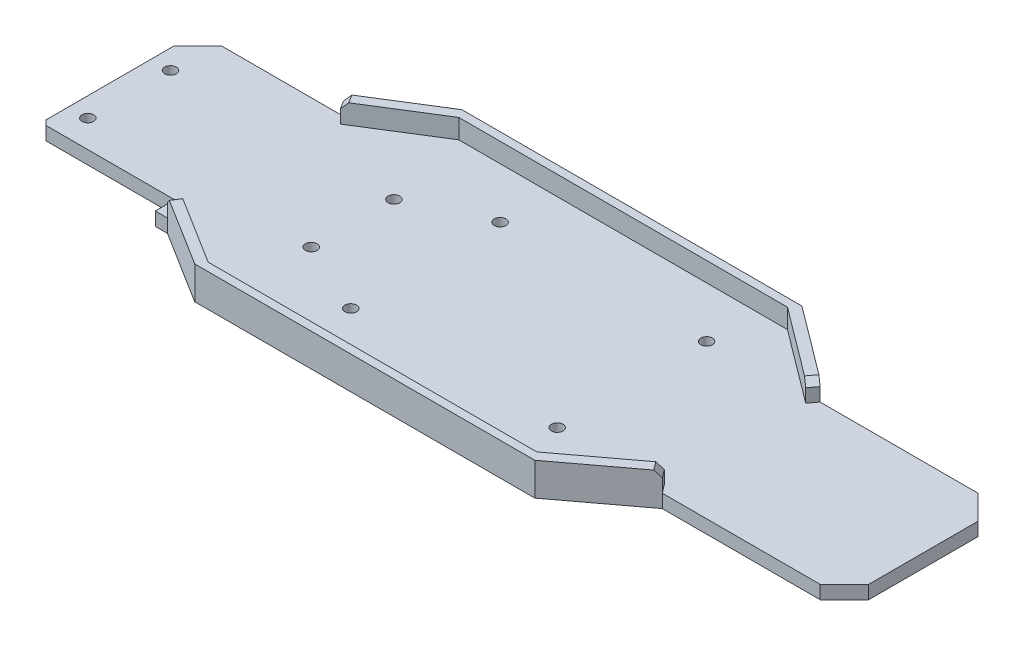
SolidWorks part; units mm, degrees
material "PETG - Polymaker"
ref_plane "Front Plane" through (0, 0, 0) normal (0, 0, 1) x (1, 0, 0)
ref_plane "Top Plane" through (0, 0, 0) normal (0, 1, 0) x (1, 0, 0)
ref_plane "Right Plane" through (0, 0, 0) normal (1, 0, 0) x (0, 0, -1)
sketch "Sketch1" plane through (0, 0, 0) normal (0, 1, 0) x (1, 0, 0)
  line L0 (-235.1499, 0) -> (235.1499, 0) construction
  line L1 (0, 0) -> (0, 52596.8311) construction
  line L2 (-100, 36.25) -> (-70, 55)
  line L3 (-70, 55) -> (70, 55)
  line L4 (-100, 36.25) -> (-160, 36.25)
  line L5 (-160, 36.25) -> (-160, -36.25)
  line L6 (-70, -55) -> (70, -55)
  line L7 (-100, -36.25) -> (-70, -55)
  line L8 (-100, -36.25) -> (-160, -36.25)
  line L9 (70, 55) -> (100, 32.5)
  line L10 (100, 32.5) -> (175, 32.5)
  line L11 (175, 32.5) -> (175, -32.5)
  line L12 (100, -32.5) -> (175, -32.5)
  line L13 (70, -55) -> (100, -32.5)
  point P3 (0, 0)
  point P10 (-85, 45.625)
  point P15 (-85, -45.625)
  point P18 (-160, 0)
  point P19 (0, -55)
  point P20 (0, 55)
  point P23 (175, 0)
  dimension "D1" = 55
  dimension "D2" = 72.5
  dimension "D3" = 30
  dimension "D4" = 60
  dimension "D5" = 140
  dimension "D6" = 75
  dimension "D7" = 65
  dimension "D8" = 30
  dimension "D9" = 110
extrude "Boss-Extrude1" add sketch "Sketch1" along normal blind 5.5
sketch "Sketch3" plane through (0, 5.5, 0) normal (0, 1, 0) x (1, 0, 0)
  line L0 (0, 0) -> (50000, 0) construction
  line L1 (0, 0) -> (0, 50000) construction
  line L2 (0, 55) -> (-70, 55)
  line L3 (70, 55) -> (-70, 55) construction
  line L4 (-70, 55) -> (-100, 36.25)
  line L5 (-100, 36.25) -> (-97.88, 32.858)
  line L6 (-97.88, 32.858) -> (-67.88, 51.608)
  line L7 (-67.88, 51.608) -> (0, 51.608)
  line L8 (-70, 55) -> (-67.88, 51.608) construction
  line L9 (0, 55) -> (70, 55)
  line L10 (70, 55) -> (100, 32.5)
  line L11 (100, 32.5) -> (97.456, 29.108)
  line L12 (97.456, 29.108) -> (67.456, 51.608)
  line L13 (67.456, 51.608) -> (0, 51.608)
  line L14 (67.456, 51.608) -> (70, 55) construction
  line L15 (67.456, -51.608) -> (70, -55) construction
  line L16 (-70, -55) -> (-67.88, -51.608) construction
  line L17 (67.456, -51.608) -> (0, -51.608)
  line L18 (97.456, -29.108) -> (67.456, -51.608)
  line L19 (100, -32.5) -> (97.456, -29.108)
  line L20 (70, -55) -> (100, -32.5)
  line L21 (0, -55) -> (70, -55)
  line L22 (-67.88, -51.608) -> (0, -51.608)
  line L23 (-97.88, -32.858) -> (-67.88, -51.608)
  line L24 (-100, -36.25) -> (-97.88, -32.858)
  line L25 (-70, -55) -> (-100, -36.25)
  line L26 (0, -55) -> (-70, -55)
  dimension "D1" = 4
extrude "Chassis-Walls1" add sketch "Sketch3" along normal blind 8
chamfer "Chamfer1" distance 10 angle 45 2 edges at (-160, 2.75, -36.25) (-160, 2.75, 36.25)
chamfer "Chamfer2" distance 10 angle 45 2 edges at (175, 2.75, -32.5) (175, 2.75, 32.5)
chamfer "Chamfer3" distance 2.5 angle 45 4 edges at (-98.94, 13.5, -34.554) (-98.94, 13.5, 34.554) (98.728, 13.5, 30.804) (98.728, 13.5, -30.804)
sketch "Sketch4" plane through (0, 0, 0) normal (0, -1, 0) x (1, 0, 0)
  line L0 (0, 0) -> (50000, 0) construction
  line L1 (-152, 17) -> (-60, 17) construction
  line L2 (-160, -26.25) -> (-160, 26.25) construction
  circle A0 centre (-152, 17) radius 2.4
  circle A1 centre (-60, 17) radius 2.4
  circle A2 centre (-60, -17) radius 2.4
  circle A3 centre (-152, -17) radius 2.4
  circle A4 centre (-30, 30.75) radius 2.4
  circle A5 centre (55, 30.75) radius 2.4
  circle A6 centre (55, -30.75) radius 2.4
  circle A7 centre (-30, -30.75) radius 2.4
  dimension "D1" = 4.8
  dimension "D2" = 4.8
  dimension "D6" = 4.8
  dimension "D8" = 4.8
  dimension "D3" = 8
  dimension "D4" = 92
  dimension "D5" = 34
  dimension "D7" = 30
  dimension "D9" = 85
  dimension "D10" = 61.5
extrude "Cut-Extrude1" cut sketch "Sketch4" against normal blind 10
sketch "Sketch5" plane through (0, 5.5, 0) normal (0, 1, 0) x (1, 0, 0)
  line L0 (-160, -28.25) -> (-105, -28.25)
  line L1 (-160, 26.25) -> (-160, -26.25) construction
  line L2 (-105, -28.25) -> (-105, -36.25)
  line L3 (-150, -36.25) -> (-100, -36.25) construction
  line L4 (-105, -36.25) -> (-160, -36.25)
  line L5 (-160, -36.25) -> (-160, -28.25)
  dimension "D1" = 55
  dimension "D2" = 8
extrude "Cut-Extrude2" cut sketch "Sketch5" against normal blind 10
equation "\"D6@Sketch4\"=\"D2@Sketch4\""
equation "\"D8@Sketch4\"=\"D2@Sketch4\""
